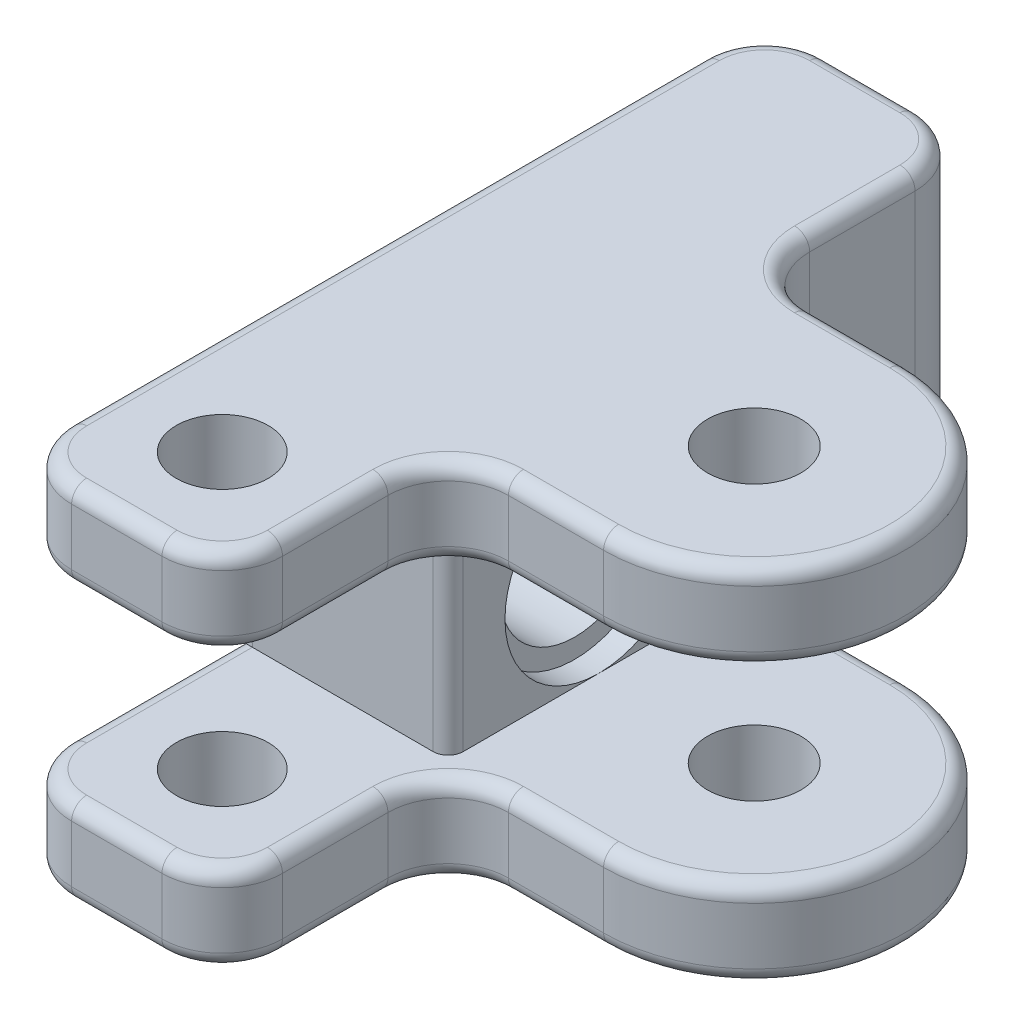
SolidWorks part; units mm, degrees
ref_plane "Front Plane" through (0, 0, 0) normal (0, 0, 1) x (1, 0, 0)
ref_plane "Top Plane" through (0, 0, 0) normal (0, 1, 0) x (1, 0, 0)
ref_plane "Right Plane" through (0, 0, 0) normal (1, 0, 0) x (0, 0, -1)
sketch "Sketch2" plane through (0, 0, 0) normal (0, 1, 0) x (1, 0, 0)
  line L0 (-5.16, -5) -> (-5.16, -12.5)
  line L1 (0, 5) -> (-5.16, 5)
  line L3 (0, -5) -> (-5.16, -5)
  line L5 (-5.16, 12.5) -> (-12.16, 12.5)
  line L6 (-5.16, 12.5) -> (-5.16, 5)
  line L7 (-5.16, -12.5) -> (-12.16, -12.5)
  line L8 (-12.16, 12.5) -> (-12.16, -12.5)
  circle A0 centre (0, 0) radius 1.55
  arc A1 (0, 5) -> (0, -5) centre (0, 0) cw
  circle A2 centre (-8.66, -9) radius 1.525
  point P10 (-12.16, 0)
  dimension "D5" = 3.1
  dimension "D6" = 3.05
  dimension "D1" = 5.16
  dimension "D2" = 10
  dimension "D3" = 7
  dimension "D4" = 25
  dimension "D7" = 3.5
extrude "Boss-Extrude1" add sketch "Sketch2" along normal blind 12
sketch "Sketch3" plane through (0, 0, 5) normal (0, 0, 1) x (1, 0, 0)
  line L0 (0, 12) -> (0, 0) construction
  line L1 (6.7543, 2.885) -> (-5.16, 2.885)
  line L2 (6.7543, 2.885) -> (6.7543, 9.115)
  line L3 (6.7543, 9.115) -> (-5.16, 9.115)
  line L4 (-5.16, 2.885) -> (-5.16, 9.115)
  line L5 (-5.16, 12) -> (-5.16, 0) construction
  point P8 (0, 6)
  point P9 (6.7543, 6)
  dimension "D1" = 6.23
extrude "Cut-Extrude1" cut sketch "Sketch3" against normal blind 12
fillet "Fillet2" radius 2 4 edges at (-5.16, 10.5575, -5) (-5.16, 1.4425, -5) (-5.16, 10.5575, 5) (-5.16, 1.4425, 5)
sketch "Sketch5" plane through (-12.16, 0, 0) normal (-1, 0, 0) x (0, 0, 1)
  circle A0 centre (0, 6) radius 2.475
  dimension "D1" = 4.95
extrude "Cut-Extrude3" cut sketch "Sketch5" against normal blind 13
sketch "Sketch6" plane through (0, 0, 12.5) normal (0, 0, 1) x (1, 0, 0)
  line L0 (-12.16, 12) -> (-12.16, 0) construction
  line L1 (-12.16, 9.115) -> (-5.16, 9.115)
  line L2 (-12.16, 9.115) -> (-12.16, 2.885)
  line L3 (-12.16, 2.885) -> (-5.16, 2.885)
  line L4 (-5.16, 9.115) -> (-5.16, 2.885)
  line L5 (0, 9.115) -> (-3.16, 9.115) construction
extrude "Cut-Extrude4" cut sketch "Sketch6" against normal up to vertex (7.5 mm away) up to point (0, 2.885, 5)
fillet "Fillet3" radius 2 5 edges at (-12.16, 6, -12.5) (-5.16, 6, -12.5) (-12.16, 10.5575, 12.5) (-5.16, 10.5575, 12.5) (-12.16, 1.4425, 12.5)
sketch "Sketch8" plane through (-5.16, 0, 0) normal (1, 0, 0) x (0, 0, -1)
  line L1 (7, 2.885) -> (-5, 2.885) construction
  circle A0 centre (0, 6) radius 3.115
  circle A2 centre (0, 6) radius 2.475
  circle A3 centre (0, 6) radius 2.475 construction
extrude "Cut-Extrude5" cut sketch "Sketch8" against normal blind 0.8
fillet "Fillet8" radius 0.5 49 edges at (-4.5742, 2.885, -5.5858) (-1.58, 2.885, -5) (5, 2.885, 0) (-1.58, 2.885, 5) (-4.5742, 2.885, 5.5858) (-12.16, 2.885, 7.75) (-11.5742, 2.885, 11.9142) (-8.66, 2.885, 12.5) (-5.7458, 2.885, 11.9142) (-4.5742, 9.115, -5.5858) (-1.58, 9.115, -5) (5, 9.115, 0) (-1.58, 9.115, 5) (-4.5742, 9.115, 5.5858) (-12.16, 9.115, 7.75) (-11.5742, 9.115, 11.9142) (-8.66, 9.115, 12.5) (-5.7458, 9.115, 11.9142) (-1.58, 12, 5) (-4.5742, 12, 5.5858) (-5.16, 12, 8.75) (-5.7458, 12, 11.9142) (-8.66, 12, 12.5) (-11.5742, 12, 11.9142) (-12.16, 12, 0) (-11.5742, 12, -11.9142) (-8.66, 12, -12.5) (-5.7458, 12, -11.9142) (-5.16, 12, -8.75) (-4.5742, 12, -5.5858) (-1.58, 12, -5) (-1.58, 0, 5) (-4.5742, 0, 5.5858) (-5.16, 0, -8.75) (-5.7458, 0, 11.9142) (-8.66, 0, 12.5) (-11.5742, 0, 11.9142) (-12.16, 0, 0) (-11.5742, 0, -11.9142) (-8.66, 0, -12.5) (-5.7458, 0, -11.9142) (-4.5742, 0, -5.5858) (-1.58, 0, -5) (-5.16, 2.885, 8.75) (-5.16, 9.115, 8.75) (5, 12, 0) (5, 0, 0) (-5.16, 6, 5) (-12.16, 6, 5)
